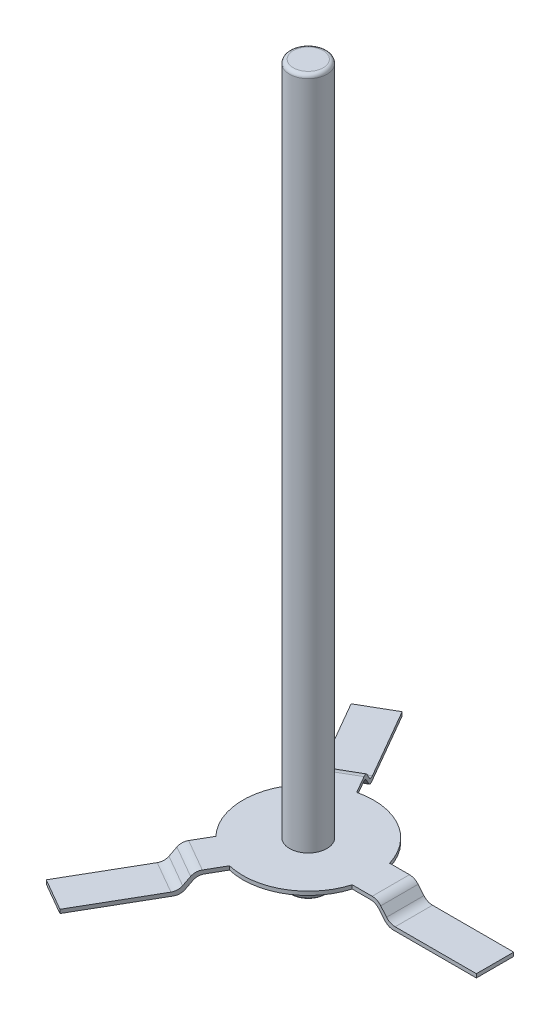
SolidWorks part; units mm, degrees
material "Ст. 3кп ГОСТ 380-2005"
ref_plane "Спереди" through (0, 0, 0) normal (0, 0, 1) x (1, 0, 0)
ref_plane "Сверху" through (0, 0, 0) normal (0, 1, 0) x (1, 0, 0)
ref_plane "Справа" through (0, 0, 0) normal (1, 0, 0) x (0, 0, -1)
sketch "Эскиз1" plane through (0, 0, 0) normal (0, 1, 0) x (1, 0, 0)
  circle A0 centre (0, 0) radius 0.5
  dimension "D1" = 1
extrude "Бобышка-Вытянуть1" add sketch "Эскиз1" along normal blind 19.15
ref_plane "Плоскость1" through (0, 1, 0) normal (0, 1, 0) x (1, 0, 0)
sketch "Эскиз2" plane through (0, 1, 0) normal (0, 1, 0) x (1, 0, 0)
  circle A0 centre (0, 0) radius 1.75
  circle A1 centre (0, 0) radius 0.5
  circle A2 centre (0, 0) radius 0.5 construction
  dimension "D1" = 3.5
extrude "Бобышка-Вытянуть2" add sketch "Эскиз2" along normal blind 0.1
sketch "Эскиз3" plane through (0, 0, 0) normal (0, 0, 1) x (1, 0, 0)
  line L0 (1.5, 1) -> (2.3034, 1)
  line L1 (2.3034, 1) -> (2.639, 0.6)
  line L2 (2.639, 0.6) -> (5, 0.6)
  line L3 (5, 0.6) -> (5, 0.7)
  line L4 (5, 0.7) -> (2.6856, 0.7)
  line L5 (2.6856, 0.7) -> (2.35, 1.1)
  line L6 (2.35, 1.1) -> (1.5, 1.1)
  line L7 (1.75, 1.1) -> (-1.75, 1.1) construction
  line L8 (-1.75, 1) -> (1.75, 1) construction
  line L9 (1.5, 1.1) -> (1.5, 1)
  line L10 (-0.5, 0) -> (0.5, 0) construction
  dimension "D1" = 5
  dimension "D2" = 2.35
  dimension "D3" = 0.1
  dimension "D4" = 130
  dimension "D5" = 1.5
  dimension "D6" = 0.6
extrude "Бобышка-Вытянуть3" add sketch "Эскиз3" along normal mid plane 1
pattern_circular "Круговой массив1" count 3 over 360 about axis through (0, 1.1, 0) along (0, 1, 0) of "Бобышка-Вытянуть3"
fillet "Скругление2" radius 0.3 12 edges at (-1.175, 1.1, -2.0352) (-1.3428, 0.7, -2.3258) (-1.3195, 0.6, -2.2854) (-1.1517, 1, -1.9948) (2.639, 0.6, 0) (2.3034, 1, 0) (2.6856, 0.7, 0) (2.35, 1.1, 0) (-1.1517, 1, 1.9948) (-1.3195, 0.6, 2.2854) (-1.3428, 0.7, 2.3258) (-1.175, 1.1, 2.0352)
fillet "Скругление3" radius 0.1 2 edges at (0, 19.15, 0.5) (0, 0, 0.5)
